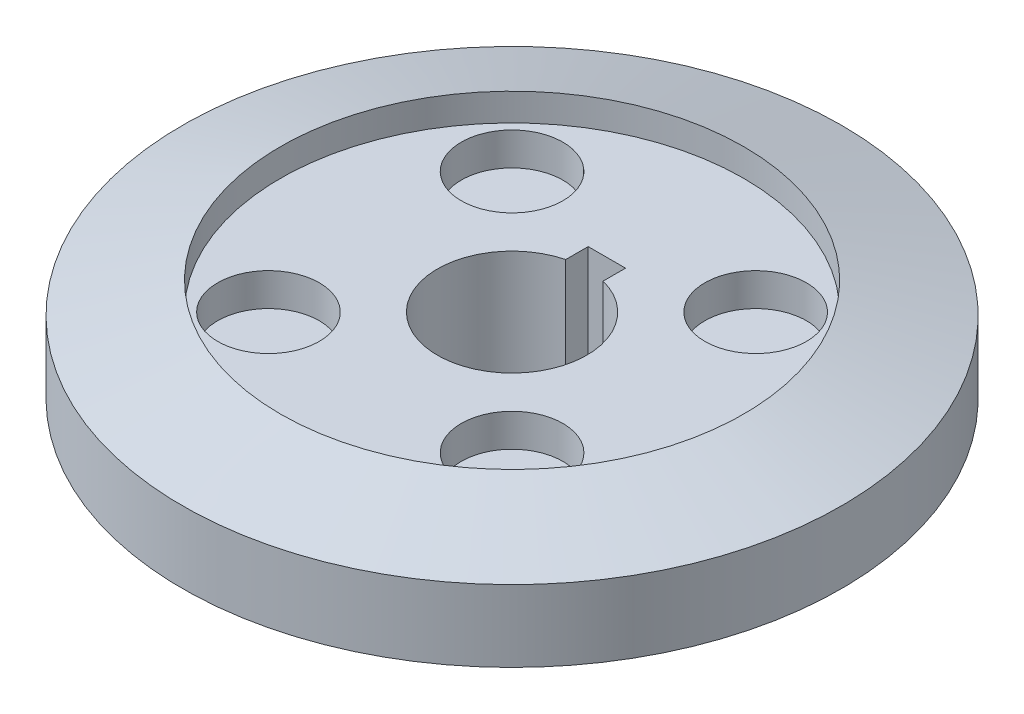
SolidWorks part; units mm, degrees
ref_plane "Front Plane" through (0, 0, 0) normal (0, 0, 1) x (1, 0, 0)
ref_plane "Top Plane" through (0, 0, 0) normal (0, 1, 0) x (1, 0, 0)
ref_plane "Right Plane" through (0, 0, 0) normal (1, 0, 0) x (0, 0, -1)
sketch "Sketch1" plane through (0, 0, 0) normal (0, 0, 1) x (1, 0, 0)
  line L0 (5, -6) -> (10.05, -6)
  line L1 (10.05, -6) -> (10.05, 0)
  line L2 (10.05, 0) -> (22.05, 0)
  line L3 (22.05, 0) -> (22.05, 4.8)
  line L4 (22.05, 4.8) -> (15.5, 6.84)
  line L5 (15.5, 6.84) -> (15.5, 5)
  line L6 (15.5, 5) -> (5, 5)
  line L7 (5, 5) -> (5, -6)
  line L8 (0, 0) -> (0, 26.7948) construction
  dimension "D1" = 44.1
  dimension "D2" = 20.1
  dimension "D3" = 10
  dimension "D4" = 31
  dimension "D5" = 6
  dimension "D6" = 4.8
  dimension "D7" = 11
  dimension "D8" = 6.84
  dimension "D9" = 17.299
revolve "Revolve1" add sketch "Sketch1" angle 360 about L8
fillet "Fillet1" radius 1.5 1 edges at (0, 0, -10.05)
sketch "Sketch2" plane through (0, 0, 0) normal (0, 1, 0) x (1, 0, 0)
  line L0 (-1.25, 4.8412) -> (-1.25, 6.3412)
  line L1 (-1.25, 6.3412) -> (1.25, 6.3412)
  line L2 (1.25, 6.3412) -> (1.25, 4.8412)
  line L3 (-1.25, 4.8412) -> (1.25, 4.8412)
  circle A0 centre (0, 0) radius 5 construction
  point P4 (0, 6.3412)
  dimension "D1" = 2.5
  dimension "D2" = 1.5
extrude "Cut-Extrude1" cut sketch "Sketch2" against normal through all and the other way through all
sketch "Sketch3" plane through (0, 5, 0) normal (0, 1, 0) x (1, 0, 0)
  line L0 (0, 0) -> (8.1494, 8.1494) construction
  line L1 (0, 0) -> (28.8934, 0) construction
  circle A0 centre (8.1494, 8.1494) radius 3.4
  dimension "D1" = 6.8
  dimension "D2" = 45
  dimension "D3" = 11.525
extrude "Cut-Extrude2" cut sketch "Sketch3" against normal blind 2.2
ref_axis "Axis1" through (0, 11.45, 0) along (0, -1, 0)
pattern_circular "CirPattern1" count 4 over 360 about axis through (0, 11.45, 0) along (0, -1, 0) of "Cut-Extrude2"
equation "\"D3@Sketch3\"=23.05/2"
